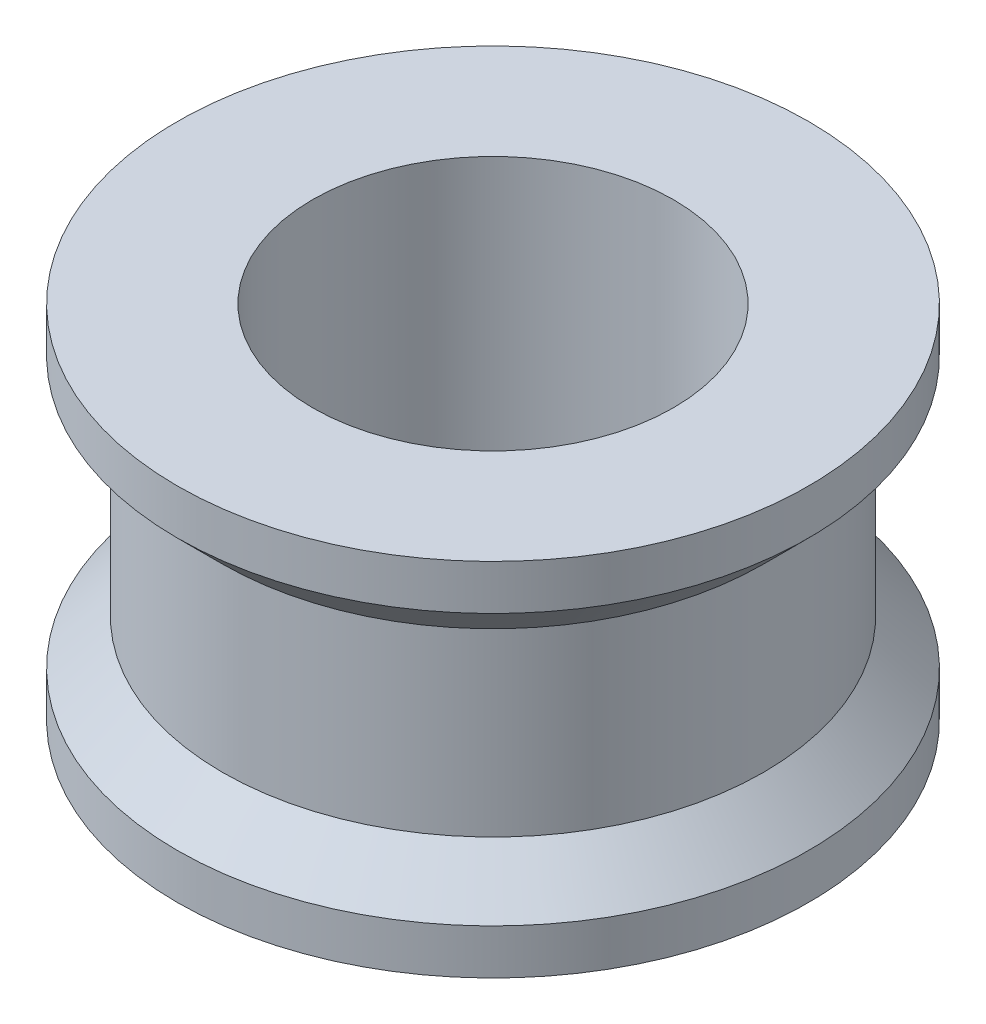
SolidWorks part; units mm, degrees
ref_plane "Front Plane" through (0, 0, 0) normal (0, 0, 1) x (1, 0, 0)
ref_plane "Top Plane" through (0, 0, 0) normal (0, 1, 0) x (1, 0, 0)
ref_plane "Right Plane" through (0, 0, 0) normal (1, 0, 0) x (0, 0, -1)
sketch "Sketch1" plane through (0, 0, 0) normal (0, 0, 1) x (1, 0, 0)
  line L0 (0, 45.4911) -> (0, 0) construction
  line L1 (2, 0) -> (3.5, 0)
  line L2 (3.5, 0) -> (3.5, 0.5)
  line L3 (3.5, 0.5) -> (3, 1)
  line L4 (3, 1) -> (3, 3)
  line L5 (3, 3) -> (3.5, 3.5)
  line L6 (3.5, 3.5) -> (3.5, 4)
  line L7 (3.5, 4) -> (2, 4)
  line L8 (2, 4) -> (2, 0)
  dimension "D1" = 2
  dimension "D2" = 3.5
  dimension "D3" = 1
  dimension "D4" = 4
  dimension "D5" = 225
  dimension "D6" = 225
  dimension "D7" = 0.5
  dimension "D8" = 0.5
revolve "Revolve1" add sketch "Sketch1" angle 360 about L0
ref_axis "Axis" through (0, 0, 0) along (0, 1, 0)
